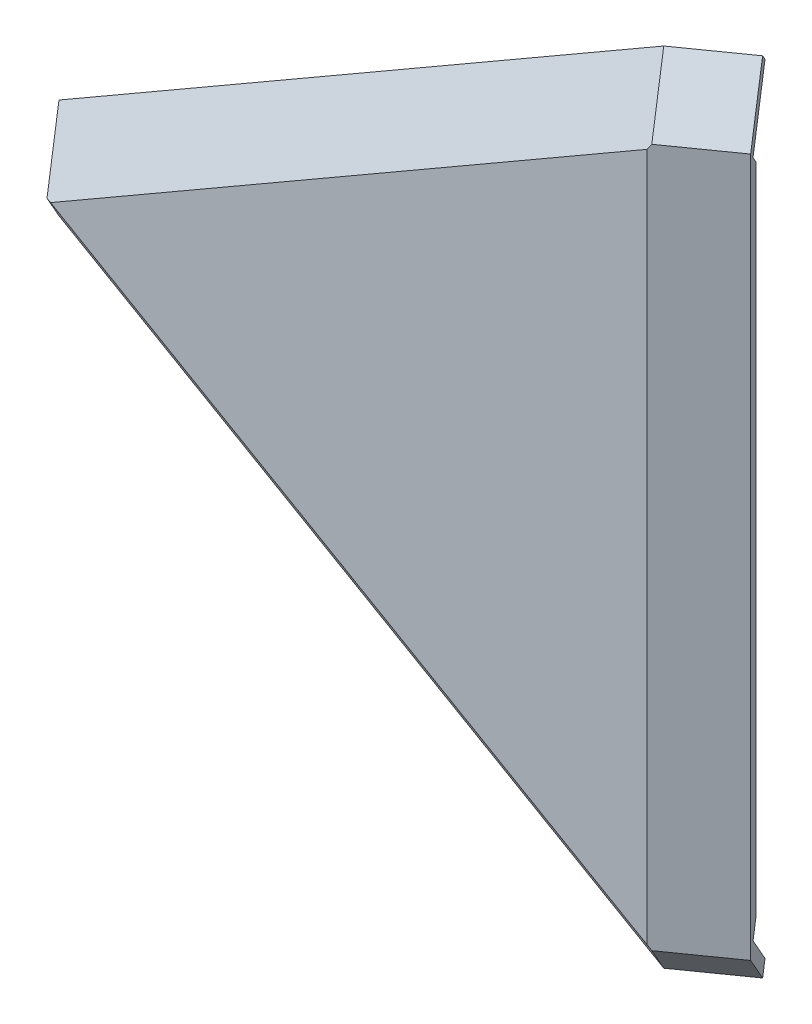
SolidWorks part; units mm, degrees
ref_plane "前基準面" through (0, 0, 0) normal (0, 0, 1) x (1, 0, 0)
ref_plane "上基準面" through (0, 0, 0) normal (0, 1, 0) x (1, 0, 0)
ref_plane "右基準面" through (0, 0, 0) normal (1, 0, 0) x (0, 0, -1)
sketch "草圖1" plane through (0, 0, 0) normal (0, 0, 1) x (1, 0, 0)
  line L0 (161.729, 200.9217) -> (161.729, 10.0028)
  line L1 (161.729, 10.0028) -> (-3.6115, 105.4623)
  line L2 (-3.6115, 105.4623) -> (161.729, 200.9217)
sketch "草圖3" plane through (-31.0463, 53.7737, -43.906) normal (0.4082, -0.7071, 0.5774) x (0.9129, 0.3162, -0.2582)
  line L0 (30.0532, 66.7002) -> (34.5254, 64.4641)
ref_axis "基準軸1" through (159.6878, 197.3861, -2.8868) along (-0.866, -0.5, 0)
ref_axis "基準軸2" through (159.6878, 197.3861, -2.8868) along (0, -1, 0)
ref_plane "平面2" through (0, 0, -2.8868) normal (0, 0, 1) x (1, 0, 0)
sketch "草圖4" plane through (0, 0, -2.8868) normal (0, 0, 1) x (1, 0, 0)
  line L0 (159.6878, 197.3861) -> (159.6878, 13.5384)
  line L1 (159.6878, 13.5384) -> (0.471, 105.4623)
  line L2 (0.471, 105.4623) -> (159.6878, 197.3861)
loft "疊層拉伸1" add profiles "草圖1", "草圖4" connector at (-3.6115, 105.4623, 0) connector at (0.471, 105.4623, -2.8868)
ref_plane "平面3" through (-15.5231, 26.8868, 43.906) normal (-0.2887, 0.5, 0.8165) x (0.9574, 0.1508, 0.2462)
sketch "草圖5" plane through (-15.5231, 26.8868, 43.906) normal (-0.2887, 0.5, 0.8165) x (0.9574, 0.1508, 0.2462)
  line L0 (12.4413, 89.9385) -> (3.9132, 108.0292)
  line L1 (12.4413, 89.9385) -> (-13.1428, 144.2106) construction
  line L2 (3.9132, 108.0292) -> (176.6058, 189.4373)
  line L3 (159.5498, 225.6186) -> (185.1338, 171.3466) construction
  line L4 (176.6058, 189.4373) -> (185.1338, 171.3466)
  line L5 (185.1338, 171.3466) -> (12.4413, 89.9385)
  point P10 (8.1772, 98.9839)
  dimension "D1" = 10
ref_plane "平面4" through (-14.5025, 25.1191, 41.0193) normal (-0.2887, 0.5, 0.8165) x (0.9574, 0.1508, 0.2462)
sketch "草圖6" plane through (-14.5025, 25.1191, 41.0193) normal (-0.2887, 0.5, 0.8165) x (0.9574, 0.1508, 0.2462)
  line L0 (15.6393, 91.4461) -> (7.1112, 109.5368)
  line L1 (15.6393, 91.4461) -> (-9.9448, 145.7181) construction
  line L2 (7.1112, 109.5368) -> (173.4078, 187.9297)
  line L3 (156.3517, 224.1111) -> (181.9358, 169.839) construction
  line L4 (173.4078, 187.9297) -> (181.9358, 169.839)
  line L5 (181.9358, 169.839) -> (15.6393, 91.4461)
  dimension "D1" = 20
loft "疊層拉伸2" add profiles "草圖5", "草圖6" connector at (153.5641, 215.0638, -11.547) connector at (151.5228, 211.5283, -14.4338)
sketch "草圖7" plane through (107.8194, 0, -76.2398) normal (0.8165, 0, -0.5774) x (-0.5774, 0, -0.8165)
  line L0 (-93.3743, 200.9217) -> (-89.8388, 197.3861)
  line L1 (-89.8388, 197.3861) -> (-89.8388, 13.5384)
  line L2 (-89.8388, 13.5384) -> (-93.3743, 10.0028)
  line L3 (-93.3743, 10.0028) -> (-93.3743, 200.9217)
extrude "填料-伸長1" add sketch "草圖7" along normal blind 20
sketch "草圖8" plane through (29.8424, 51.6886, 42.2035) normal (-0.4082, -0.7071, -0.5774) x (0.9129, -0.3162, -0.2582)
  line L0 (-32.1748, -68.9363) -> (-36.647, -66.7002)
  line L1 (-36.647, -66.7002) -> (-32.1748, -68.9363) construction
  line L2 (-36.647, -66.7002) -> (84.1007, -127.074) construction
  line L3 (-36.647, -66.7002) -> (144.4746, -6.3264)
  line L4 (144.4746, -6.3264) -> (142.2385, -10.7985)
  line L5 (142.2385, -10.7985) -> (-32.1748, -68.9363)
extrude "填料-伸長2" add sketch "草圖8" along normal blind 20
other "移動面1" face at (173.9765, 81.5974, -8.6603) face at (52.2675, 59.0584, -8.6603) face at (106.6155, 105.4623, 0) face at (116.3114, 184.1279, -5.7735) offset 3 parameters "D1"=3
ref_plane "平面5" through (-5.8718, 0, 4.152) normal (-0.8165, 0, 0.5774) x (0.5774, 0, 0.8165)
sketch "草圖10" plane through (-5.8718, 0, 4.152) normal (-0.8165, 0, 0.5774) x (0.5774, 0, 0.8165)
  line L0 (-2.0851, 105.4623) -> (-16.2273, 91.3201)
  line L1 (-16.2273, 91.3201) -> (-30.3694, 105.4623)
  line L2 (-30.3694, 105.4623) -> (75.6966, 211.5283) construction
  line L3 (-30.3694, 105.4623) -> (75.6966, -0.6038) construction
  line L4 (-30.3694, 105.4623) -> (-16.2273, 119.6044)
  line L5 (-16.2273, 119.6044) -> (-2.0851, 105.4623)
extrude "填料-伸長4" add sketch "草圖10" against normal blind 4
ref_plane "平面6" through (25.7993, -44.6857, 36.4857) normal (0.4082, -0.7071, 0.5774) x (-0.9129, -0.3162, 0.2582)
sketch "草圖11" plane through (25.7993, -44.6857, 36.4857) normal (0.4082, -0.7071, 0.5774) x (-0.9129, -0.3162, 0.2582)
  line L0 (-150.8009, -6.3264) -> (-141.8566, 11.5622)
  line L1 (-141.8566, 11.5622) -> (-159.7452, 20.5065)
  line L2 (-159.7452, 20.5065) -> (-168.6895, 2.6179)
  line L3 (-168.6895, 2.6179) -> (-150.8009, -6.3264)
extrude "填料-伸長5" add sketch "草圖11" against normal blind 4
ref_plane "平面7" through (86.688, 150.148, 122.5953) normal (0.4082, 0.7071, 0.5774) x (0.9129, -0.3162, -0.2582)
sketch "草圖12" plane through (86.688, 150.148, 122.5953) normal (0.4082, 0.7071, 0.5774) x (0.9129, -0.3162, -0.2582)
  line L0 (84.1007, 127.074) -> (101.9893, 136.0183)
  line L1 (101.9893, 136.0183) -> (93.045, 153.9068)
  line L2 (93.045, 153.9068) -> (-41.1191, 86.8248) construction
  line L3 (93.045, 153.9068) -> (160.127, 19.7428) construction
  line L4 (93.045, 153.9068) -> (75.1564, 144.9626)
  line L5 (84.1007, 127.074) -> (75.1564, 144.9626) construction
  line L6 (75.1564, 144.9626) -> (84.1007, 127.074)
extrude "填料-伸長6" add sketch "草圖12" against normal blind 4
